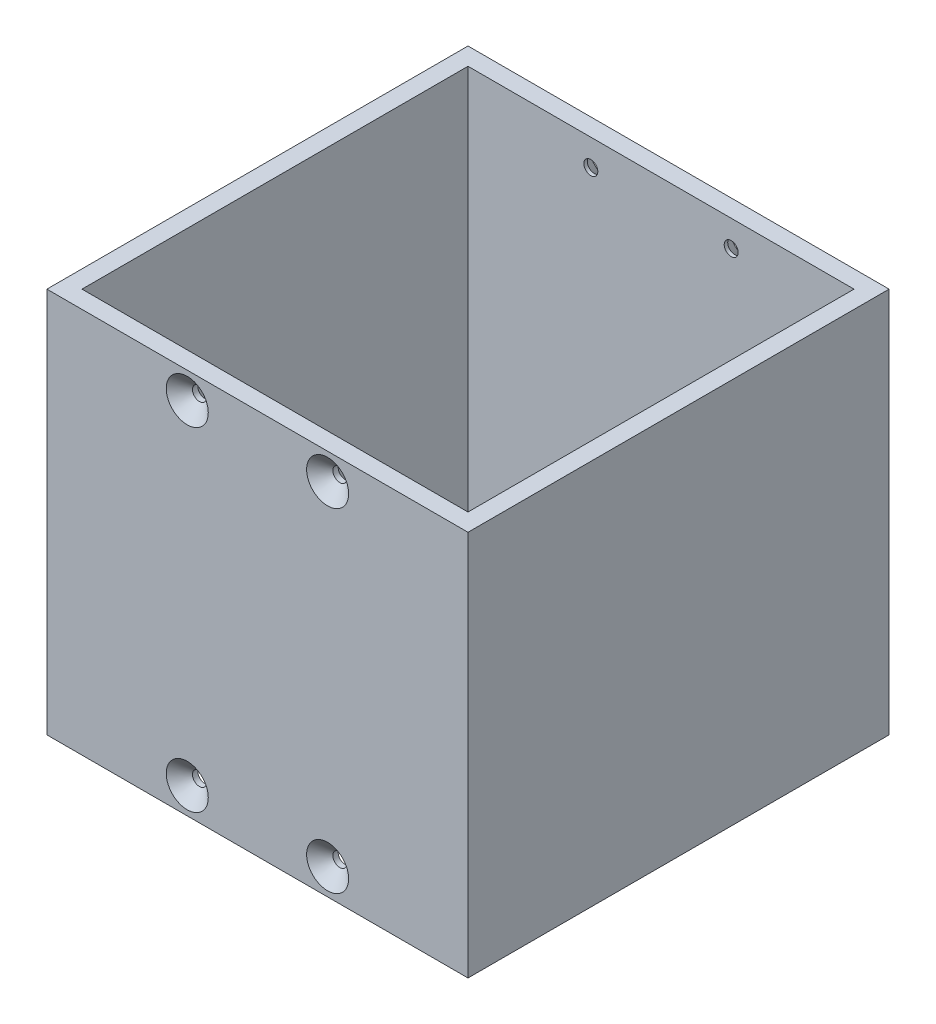
SolidWorks part; units mm, degrees
material "6061-T6 (SS)"
ref_plane "Front Plane" through (0, 0, 0) normal (0, 0, 1) x (1, 0, 0)
ref_plane "Top Plane" through (0, 0, 0) normal (0, 1, 0) x (1, 0, 0)
ref_plane "Right Plane" through (0, 0, 0) normal (1, 0, 0) x (0, 0, -1)
sketch "Sketch1" plane through (0, 0, 0) normal (0, 1, 0) x (1, 0, 0)
  line L1 (-38.1, -38.1) -> (38.1, -38.1)
  line L2 (-38.1, -38.1) -> (-38.1, 38.1)
  line L3 (-38.1, 38.1) -> (38.1, 38.1)
  line L4 (38.1, -38.1) -> (38.1, 38.1)
  line L5 (-38.1, -38.1) -> (38.1, 38.1) construction
  line L6 (-38.1, 38.1) -> (38.1, -38.1) construction
  line L7 (-34.925, -34.925) -> (34.925, -34.925)
  line L8 (-34.925, -34.925) -> (-34.925, 34.925)
  line L9 (-34.925, 34.925) -> (34.925, 34.925)
  line L10 (34.925, -34.925) -> (34.925, 34.925)
  line L11 (-34.925, -34.925) -> (34.925, 34.925) construction
  line L12 (-34.925, 34.925) -> (34.925, -34.925) construction
  point P0 (0, 0)
  point P6 (0, 0)
  dimension "D1" = 76.2
  dimension "D2" = 76.2
  dimension "D3" = 3.175
extrude "Boss-Extrude1" add sketch "Sketch1" along normal blind 9.525
sketch "Sketch2" plane through (0, 0, 38.1) normal (0, 0, 1) x (1, 0, 0)
  line L0 (-38.1, 0) -> (38.1, 0) construction
  circle A0 centre (-12.7, 4.7625) radius 1.2637
  circle A1 centre (12.7, 4.7625) radius 1.2637
  dimension "D4" = 2.5273
  dimension "D1" = 4.7625
  dimension "D2" = 12.7
  dimension "D3" = 12.7
extrude "Cut-Extrude1" cut sketch "Sketch2" against normal through all
chamfer "Chamfer1" distance 2.54 angle 41 4 edges at (-11.4363, 4.7625, -38.1) (13.9636, 4.7625, -38.1) (13.9636, 4.7625, 38.1) (-11.4363, 4.7625, 38.1) first distance on face at (-11.4363, 4.7625, -34.925) first distance on face at (13.9636, 4.7625, -34.925) first distance on face at (13.9636, 4.7625, 38.1)
sketch "Sketch3" plane through (0, 9.525, 0) normal (0, 1, 0) x (1, 0, 0)
  line L0 (-34.925, 34.925) -> (-34.925, -34.925) construction
  line L1 (-34.925, -34.925) -> (34.925, -34.925) construction
  line L2 (34.925, 34.925) -> (-34.925, 34.925) construction
  line L3 (34.925, -34.925) -> (34.925, 34.925) construction
  line L4 (38.1, -38.1) -> (38.1, 38.1)
  line L5 (38.1, 38.1) -> (-38.1, 38.1)
  line L6 (-38.1, 38.1) -> (-38.1, -38.1)
  line L7 (-38.1, -38.1) -> (38.1, -38.1)
  line L8 (38.1, -38.1) -> (38.1, 38.1)
  line L9 (38.1, 38.1) -> (-38.1, 38.1)
  line L10 (-38.1, 38.1) -> (-38.1, -38.1)
  line L11 (-38.1, -38.1) -> (38.1, -38.1)
  line L12 (-34.925, 34.925) -> (-34.925, -34.925)
  line L13 (-34.925, -34.925) -> (34.925, -34.925)
  line L14 (34.925, 34.925) -> (-34.925, 34.925)
  line L15 (34.925, -34.925) -> (34.925, 34.925)
  dimension "D1" = 0
extrude "Boss-Extrude2" add sketch "Sketch3" along normal blind 25.4
mirror "Mirror2" about plane through (0, 34.925, 0) normal (0, 1, 0) of bodies 103
ref_axis "Axis1" through (0, 73.3425, 0) along (0, -1, 0)
equation "\"D3@Sketch2\"=\"D2@Sketch2\""
equation "\"D1@Sketch1\"=\"D2@Sketch1\""
